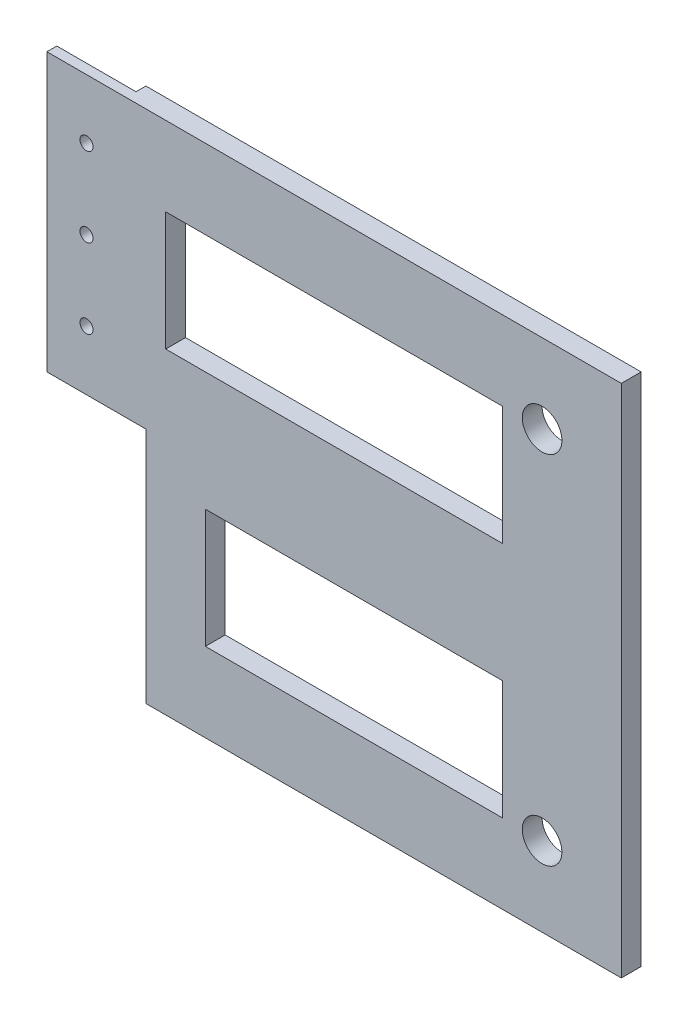
SolidWorks part; units mm, degrees
ref_plane "Front Plane" through (0, 0, 0) normal (0, 0, 1) x (1, 0, 0)
ref_plane "Top Plane" through (0, 0, 0) normal (0, 1, 0) x (1, 0, 0)
ref_plane "Right Plane" through (0, 0, 0) normal (1, 0, 0) x (0, 0, -1)
sketch "Sketch2" plane through (0, 0, 0) normal (0, 0, 1) x (1, 0, 0)
  line L4 (184.15, -82.55) -> (184.15, 82.55)
  line L6 (0, -6.35) -> (0, 82.55)
  line L8 (31.75, -6.35) -> (31.75, -82.55)
  line L9 (31.75, -82.55) -> (184.15, -82.55)
  line L11 (0, -6.35) -> (31.75, -6.35)
  line L13 (0, 82.55) -> (184.15, 82.55)
  point P0 (0, 0)
  dimension "D1" = 165.1
extrude "Boss-Extrude1" add sketch "Sketch2" along normal blind 6.35 contours L4 L13 L6 L11 L8 L9
sketch "Sketch5" plane through (0, 0, 6.35) normal (0, 0, 1) x (1, 0, 0)
  line L0 (184.15, -82.55) -> (184.15, 82.55) construction
  line L1 (-184.15, -82.55) -> (-69.85, -82.55) construction
  line L2 (31.75, -82.55) -> (184.15, -82.55) construction
  line L3 (-184.15, -82.55) -> (-184.15, 82.55) construction
  line L4 (-184.15, 82.55) -> (184.15, 82.55) construction
  circle A0 centre (-158.75, 57.15) radius 6.35
  circle A1 centre (-158.75, -57.15) radius 6.35
  circle A2 centre (158.75, 57.15) radius 6.35
  circle A3 centre (158.75, -57.15) radius 6.35
  dimension "D1" = 317.5
  dimension "D2" = 317.5
  dimension "D3" = 25.4
  dimension "D4" = 25.4
  dimension "D5" = 25.4
  dimension "D6" = 25.4
  dimension "D7" = 25.4
  dimension "D8" = 25.4
extrude "Cut-Extrude1" cut sketch "Sketch5" against normal through all contours A0 | A1 | A2 | A3
sketch "Sketch6" plane through (0, 0, 6.35) normal (0, 0, 1) x (1, 0, 0)
  line L18 (0, -927.291) -> (0, 49072.709) construction
  line L28 (50.8, -19.05) -> (50.8, -57.15)
  line L29 (146.05, -57.15) -> (50.8, -57.15)
  line L30 (146.05, -19.05) -> (146.05, -57.15)
  line L31 (146.05, -19.05) -> (50.8, -19.05)
  line L32 (38.1, 57.15) -> (38.1, 19.05)
  line L33 (146.05, 19.05) -> (38.1, 19.05)
  line L34 (146.05, 57.15) -> (146.05, 19.05)
  line L35 (146.05, 57.15) -> (38.1, 57.15)
  line L36 (0, 82.55) -> (184.15, 82.55) construction
  line L37 (184.15, -82.55) -> (184.15, 82.55) construction
  line L38 (31.75, -6.35) -> (31.75, -82.55) construction
  line L39 (31.75, -82.55) -> (184.15, -82.55) construction
  point P1 (38.1, 38.1)
  dimension "D2" = 38.1
  dimension "D3" = 38.1
  dimension "D4" = 25.4
  dimension "D5" = 38.1
  dimension "D6" = 19.05
  dimension "D7" = 38.1
  dimension "D8" = 25.4
  dimension "D11" = 0
extrude "Cut-Extrude2" cut sketch "Sketch6" against normal blind 10.16 contours L34 L35 L32 L33 | L31 L28 L29 L30 region at (92.075, 38.1, 6.35)
sketch "Sketch7" plane through (0, 0, 0) normal (0, 0, -1) x (-1, 0, 0)
  line L0 (0, -6.35) -> (-31.75, -6.35) construction
  line L1 (0, 82.55) -> (-25.4, 82.55)
  line L2 (0, 82.55) -> (0, -6.35)
  line L3 (0, -6.35) -> (-25.4, -6.35)
  line L4 (-25.4, 82.55) -> (-25.4, -6.35)
  dimension "D1" = 25.4
extrude "Cut-Extrude3" cut sketch "Sketch7" against normal blind 3.175
hole_wizard "M5x0.8 Tapped Hole1" positions "Sketch9" profile "Sketch8" tap size "M5x0.8" standard "ANSI Metric"
sketch "Sketch9" plane through (0, 0, 3.175) normal (0, 0, -1) x (-1, 0, 0)
  line L0 (0, 82.55) -> (-25.4, 82.55) construction
  line L3 (0, -6.35) -> (0, 82.55) construction
  point P0 (-12.7, 38.1)
  point P1 (-12.7, 63.5)
  point P3 (-12.7, 12.7)
  point P14 (-2.6709, 86.5742)
  dimension "D1" = 25.4
  dimension "D2" = 25.4
  dimension "D3" = 19.05
  dimension "D4" = 12.7
sketch "Sketch8" plane through (12.7, 38.1, 3.175) normal (1, 0, 0) x (0, 1, 0)
  line L0 (0, 0) -> (0, 15.2318)
  line L1 (0, 15.2318) -> (2.1, 13.97)
  line L2 (2.1, 13.97) -> (2.1, 0)
  line L5 (2.1, 0) -> (0, 0)
  line L10 (0, 15.2318) -> (-2.1, 13.97) construction
  line L11 (0, -6.35) -> (0, 107.95) construction
  dimension "Tap Drill Dia." = 4.2
  dimension "Tap Drill Depth" = 13.97
  dimension "Drill Angle" = 118
cosmetic thread "Hole Thread1" parameters "D1"=3.81, "D2"=5
cosmetic thread "Hole Thread2" parameters "D1"=3.81, "D2"=5
cosmetic thread "Hole Thread3" parameters "D1"=3.81, "D2"=5
